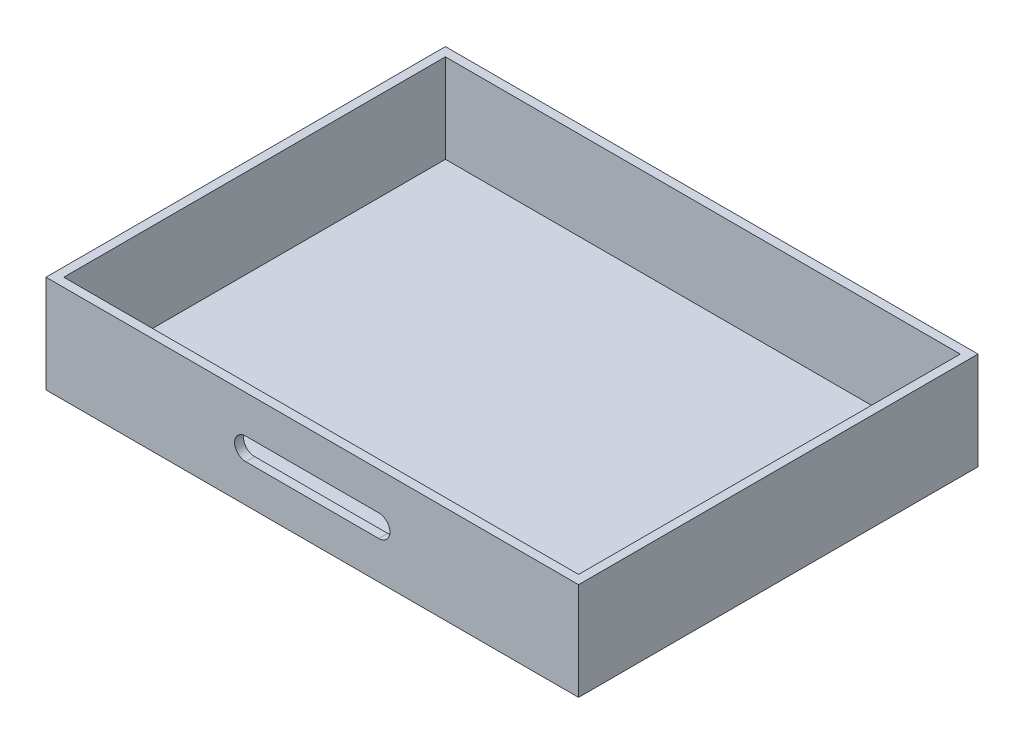
SolidWorks part; units mm, degrees
ref_plane "Plano frontal" through (0, 0, 0) normal (0, 0, 1) x (1, 0, 0)
ref_plane "Plano superior" through (0, 0, 0) normal (0, 1, 0) x (1, 0, 0)
ref_plane "Plano direito" through (0, 0, 0) normal (1, 0, 0) x (0, 0, -1)
sketch "Esboço1" plane through (0, 0, 0) normal (0, 1, 0) x (1, 0, 0)
  line L1 (-60, -45) -> (60, -45)
  line L2 (-60, -45) -> (-60, 45)
  line L3 (-60, 45) -> (60, 45)
  line L4 (60, -45) -> (60, 45)
  line L5 (-60, -45) -> (60, 45) construction
  line L6 (-60, 45) -> (60, -45) construction
  line L11 (-58.077, -43.5578) -> (53.4547, 40.091) construction
  line L12 (-58, 38.6667) -> (58, -38.6667) construction
  point P0 (0, 0)
  point P6 (0, 0)
  point P11 (0, 0)
  point P12 (0, 0)
  dimension "D1" = 120
  dimension "D2" = 90
extrude "Ressalto-extrusão2" add sketch "Esboço1" along normal blind 2
sketch "Esboço2" plane through (0, 2, 0) normal (0, 1, 0) x (1, 0, 0)
  line L1 (-58, -43) -> (58, -43)
  line L2 (-58, -43) -> (-58, 43)
  line L3 (-58, 43) -> (58, 43)
  line L4 (58, -43) -> (58, 43)
  line L5 (-58, -43) -> (58, 43) construction
  line L6 (-58, 43) -> (58, -43) construction
  point P0 (0, 0)
  dimension "D1" = 116
  dimension "D2" = 86
extrude "Extrusão-Fina1" add sketch "Esboço2" along normal blind 20 thin thin type one direction wall 2
sketch "Esboço3" plane through (0, 0, 45) normal (0, 0, 1) x (1, 0, 0)
  line L0 (0, 0) -> (0, 22) construction
  line L1 (-60, 0) -> (60, 0) construction
  line L2 (-60, 22) -> (60, 22) construction
  line L3 (-60, 11) -> (60, 11) construction
  line L4 (-60, 22) -> (-60, 0) construction
  line L5 (60, 22) -> (60, 0) construction
  line L6 (-15, 11) -> (15, 11) construction
  line L7 (-15, 13.5) -> (15, 13.5)
  line L8 (-15, 8.5) -> (15, 8.5)
  arc A0 (-15, 13.5) -> (-15, 8.5) centre (-15, 11) ccw
  arc A1 (15, 8.5) -> (15, 13.5) centre (15, 11) ccw
  point P14 (0, 11)
  dimension "D1" = 30
  dimension "D2" = 5
extrude "Corte-extrusão1" cut sketch "Esboço3" against normal up to surface (2 mm away) up to face at (0, 12, 43)
